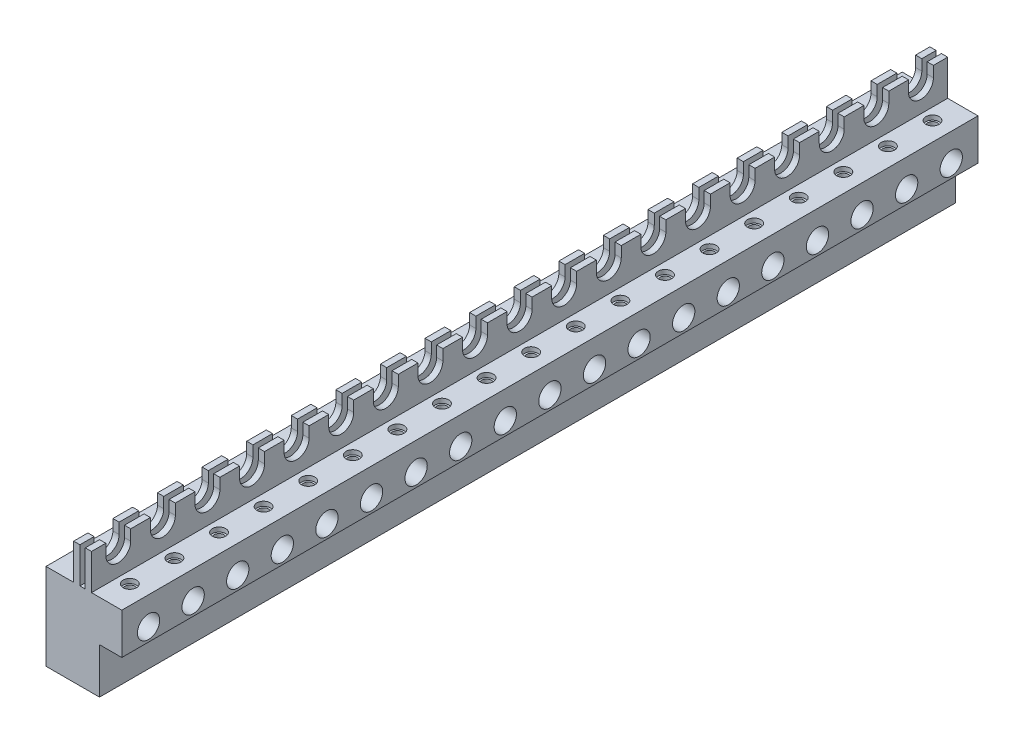
SolidWorks part; units mm, degrees
ref_plane "Front Plane" through (0, 0, 0) normal (0, 0, 1) x (1, 0, 0)
ref_plane "Top Plane" through (0, 0, 0) normal (0, 1, 0) x (1, 0, 0)
ref_plane "Right Plane" through (0, 0, 0) normal (1, 0, 0) x (0, 0, -1)
sketch "Sketch1" plane through (0, 0, 0) normal (0, 0, 1) x (1, 0, 0)
  line L1 (-4.25, -6.85) -> (4.25, -6.85)
  line L2 (-4.25, -6.85) -> (-4.25, 6.85)
  line L3 (-4.25, 6.85) -> (4.25, 6.85)
  line L4 (4.25, -6.85) -> (4.25, 6.85)
  line L5 (-4.25, -6.85) -> (4.25, 6.85) construction
  line L6 (-4.25, 6.85) -> (4.25, -6.85) construction
  point P0 (0, 0)
  dimension "D1" = 8.5
  dimension "D2" = 13.7
extrude "Boss-Extrude1" add sketch "Sketch1" against normal blind 96
sketch "Sketch2" plane through (0, 0, 0) normal (0, 0, 1) x (1, 0, 0)
  line L0 (4.25, 6.85) -> (-4.25, 6.85) construction
  line L1 (4.25, -6.85) -> (1.75, -6.85)
  line L2 (4.25, -6.85) -> (4.25, -1.75)
  line L3 (4.25, -1.75) -> (1.75, -1.75)
  line L4 (1.75, -6.85) -> (1.75, -1.75)
  line L5 (-4.25, 6.85) -> (-4.25, -6.85) construction
  dimension "D1" = 8.6
  dimension "D2" = 6
extrude "Cut-Extrude1" cut sketch "Sketch2" against normal through all
sketch "Sketch3" plane through (0, 0, 0) normal (0, 0, 1) x (1, 0, 0)
  line L0 (4.25, -1.75) -> (1.75, -1.75) construction
  line L1 (-4.25, 6.85) -> (-1.15, 6.85)
  line L2 (-4.25, 6.85) -> (-4.25, 2.85)
  line L3 (-4.25, 2.85) -> (-1.15, 2.85)
  line L4 (-1.15, 6.85) -> (-1.15, 2.85)
  line L5 (4.25, 6.85) -> (0.85, 6.85)
  line L6 (4.25, 6.85) -> (4.25, 2.85)
  line L7 (4.25, 2.85) -> (0.85, 2.85)
  line L8 (0.85, 6.85) -> (0.85, 2.85)
  line L9 (4.25, 6.85) -> (-4.25, 6.85) construction
  line L10 (-0.45, 6.85) -> (0.15, 6.85)
  line L11 (-0.45, 6.85) -> (-0.45, 2.85)
  line L12 (-0.45, 2.85) -> (0.15, 2.85)
  line L13 (0.15, 6.85) -> (0.15, 2.85)
  line L14 (-0.15, 2.85) -> (-0.15, 6.85) construction
  dimension "D1" = 4.6
  dimension "D2" = 4.1
  dimension "D3" = 2
  dimension "D4" = 0.6
  dimension "D5" = 1
extrude "Cut-Extrude2" cut sketch "Sketch3" against normal through all
sketch "Sketch4" plane through (0.85, 0, 0) normal (1, 0, 0) x (0, 0, -1)
  line L0 (1.6, 6.85) -> (1.6, 5.65)
  line L1 (96, 6.85) -> (0, 6.85) construction
  line L2 (4.4, 5.65) -> (4.4, 6.85)
  line L3 (4.4, 6.85) -> (1.6, 6.85)
  line L4 (0, 6.85) -> (0, 2.85) construction
  arc A0 (1.6, 5.65) -> (4.4, 5.65) centre (3, 5.65) ccw
  dimension "D1" = 2.6
  dimension "D2" = 1.6
  dimension "D3" = 2.8
extrude "Cut-Extrude3" cut sketch "Sketch4" against normal through all
pattern_linear "LPattern1" count 19 spacing 5 along (0, 0, -1) of "Cut-Extrude3"
sketch "Sketch5" plane through (4.25, 0, 0) normal (1, 0, 0) x (0, 0, -1)
  line L1 (3, 5.65) -> (3, -2.2393) construction
  circle A0 centre (3, -0.25) radius 1.25
  arc A2 (1.6, 5.65) -> (4.4, 5.65) centre (3, 5.65) ccw construction
  dimension "D1" = 5.9
  dimension "D2" = 2.5
extrude "Cut-Extrude4" cut sketch "Sketch5" against normal through all
pattern_linear "LPattern2" count 19 spacing 5 along (0, 0, -1) of "Cut-Extrude4"
hole_wizard "Ø1.8 (1.8) Diameter Hole1" positions "Sketch9" profile "Sketch10" hole size "Ø1.8" standard "DIN"
sketch "Sketch9" plane through (0, 2.85, 0) normal (0, 1, 0) x (-1, 0, 0)
  line L0 (0.8, -1.6) -> (0.8, -4.4) construction
  line L1 (1.15, -1.6) -> (0.45, -1.6) construction
  line L2 (1.15, -4.4) -> (0.45, -4.4) construction
  line L3 (0.8, -3) -> (5.4547, -3) construction
  line L4 (0.45, -3) -> (-0.15, -3) construction
  line L5 (0.45, -1.6) -> (0.45, -4.4) construction
  line L6 (-0.15, -4.4) -> (-0.15, -1.6) construction
  line L7 (0.15, -3) -> (0.15, 0.2827) construction
  point P0 (2.85, -3)
  dimension "D1" = 2.7
sketch "Sketch10" plane through (-2.85, 2.85, -3) normal (1, 0, 0) x (0, 0, 1)
  line L0 (0, 0) -> (0, 8.4552)
  line L1 (0, 8.4552) -> (0.9, 7.7)
  line L2 (0.9, 7.7) -> (0.9, 0)
  line L5 (0.9, 0) -> (0, 0)
  line L10 (0, 8.4552) -> (-0.9, 7.7) construction
  line L11 (0, -6.35) -> (0, 107.95) construction
  dimension "Hole Dia." = 1.8
  dimension "Hole Depth" = 7.7
  dimension "Drill Angle" = 100
pattern_linear "LPattern3" count 19 spacing 5 along (0, 0, -1) of "Ø1.8 (1.8) Diameter Hole1"
hole_wizard "M1.4x0.3 Tapped Hole1" positions "Sketch12" profile "Sketch13" tap size "M1.4x0.3" standard "ANSI Metric" end condition up to next
sketch "Sketch12" plane through (0, 2.85, 0) normal (0, 1, 0) x (-1, 0, 0)
  line L0 (2.85, -3) -> (-5.8661, -3) construction
  circle A0 centre (2.85, -3) radius 0.9 construction
  point P0 (-2.15, -3)
  dimension "D1" = 5
sketch "Sketch13" plane through (2.15, 2.85, -3) normal (1, 0, 0) x (0, 0, 1)
  line L0 (0, 0) -> (0, 4.6)
  line L1 (0, 4.6) -> (0.55, 4.6)
  line L2 (0.55, 4.6) -> (0.55, 0)
  line L5 (0.55, 0) -> (0, 0)
  line L11 (0, -6.35) -> (0, 107.95) construction
  dimension "Thru Tap Drill Dia." = 1.1
  dimension "Thru Tap Drill Depth" = 4.6
cosmetic thread "Hole Thread1" parameters "D2"=1.4
sketch "Sketch14" plane through (0, 2.85, 0) normal (0, 1, 0) x (1, 0, 0)
  circle A0 centre (2.15, 3) radius 0.75
  dimension "D1" = 1.5
extrude "Cut-Extrude5" cut sketch "Sketch14" against normal blind 0.5
pattern_linear "LPattern4" count 19 spacing 5 along (0, 0, -1) of "M1.4x0.3 Tapped Hole1", "Cut-Extrude5"
